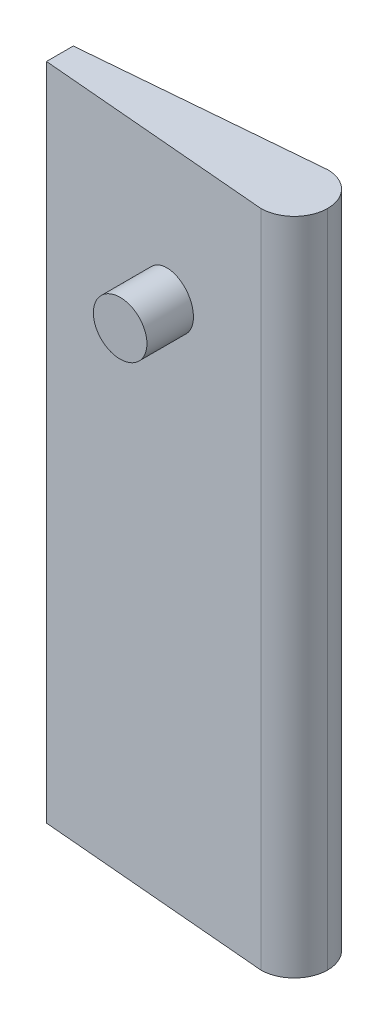
SolidWorks part; units mm, degrees
other "Markup1"
sketch "Sketch8"
ref_plane "Front Plane" through (0, 0, 0) normal (0, 0, 1) x (1, 0, 0)
ref_plane "Top Plane" through (0, 0, 0) normal (0, 1, 0) x (1, 0, 0)
ref_plane "Right Plane" through (0, 0, 0) normal (1, 0, 0) x (0, 0, -1)
sketch "Sketch1" plane through (0, 0, 0) normal (0, 0, 1) x (1, 0, 0)
  line L1 (-10, 0) -> (-10, 49.25)
  line L2 (10, 0) -> (10, 49.25)
  line L4 (-10, 49.25) -> (10, 49.25)
  line L5 (-10, 0) -> (10, 0)
  point P0 (0, 0)
  dimension "D2" = 20
  dimension "D7" = 20
  dimension "D9" = 49.25
extrude "Boss-Extrude1" add sketch "Sketch1" along normal mid plane 5
ref_plane "Plane1" through (0, 0, 0) normal (0, 0, 1) x (1, 0, 0)
sketch "Sketch13" plane through (0, 0, 2.5) normal (0, 0, 1) x (1, 0, 0)
  line L0 (10, 49.25) -> (-10, 49.25) construction
  point P0 (0, 39.25)
  point P3 (0, 49.25)
  dimension "D1" = 10
fillet "Fillet3" radius 2.5 2 edges at (10, 24.625, 2.5) (10, 24.625, -2.5)
sketch "Sketch11" plane through (0, 49.25, 0) normal (0, 1, 0) x (1, 0, 0)
  line L0 (7.5, 2.5) -> (-10, 1)
  line L1 (-10, -2.5) -> (-10, 2.5) construction
  line L2 (-10, 1) -> (-10, -1)
  line L3 (-10, -1) -> (7.5, -2.5)
  arc A0 (7.5, -2.5) -> (10, 0) centre (7.5, 0) ccw construction
  arc A1 (10, 0) -> (7.5, 2.5) centre (7.5, 0) ccw construction
  arc A2 (7.5, -2.5) -> (10, 0) centre (7.5, 0) ccw
  arc A3 (10, 0) -> (7.5, 2.5) centre (7.5, 0) ccw
  line M7 (-10, -2.5) -> (7.5, -2.5)
  line M11 (7.5, 2.5) -> (-10, 2.5)
  line M12 (-10, 2.5) -> (-10, -2.5)
  dimension "D1" = 2
extrude "Cut-Extrude1" cut sketch "Sketch11" against normal through all contours L0 M11 M12 | L3 M12 M7 region at (-4.1667, 49.25, -2) region at (-4.1667, 49.25, 2)
sketch "Sketch14" plane through (0, 0, 0) normal (0, 0, 1) x (1, 0, 0)
  circle A0 centre (0, 39.25) radius 2
  dimension "D1" = 4
extrude "Boss-Extrude2" add sketch "Sketch14" along normal mid plane 11
